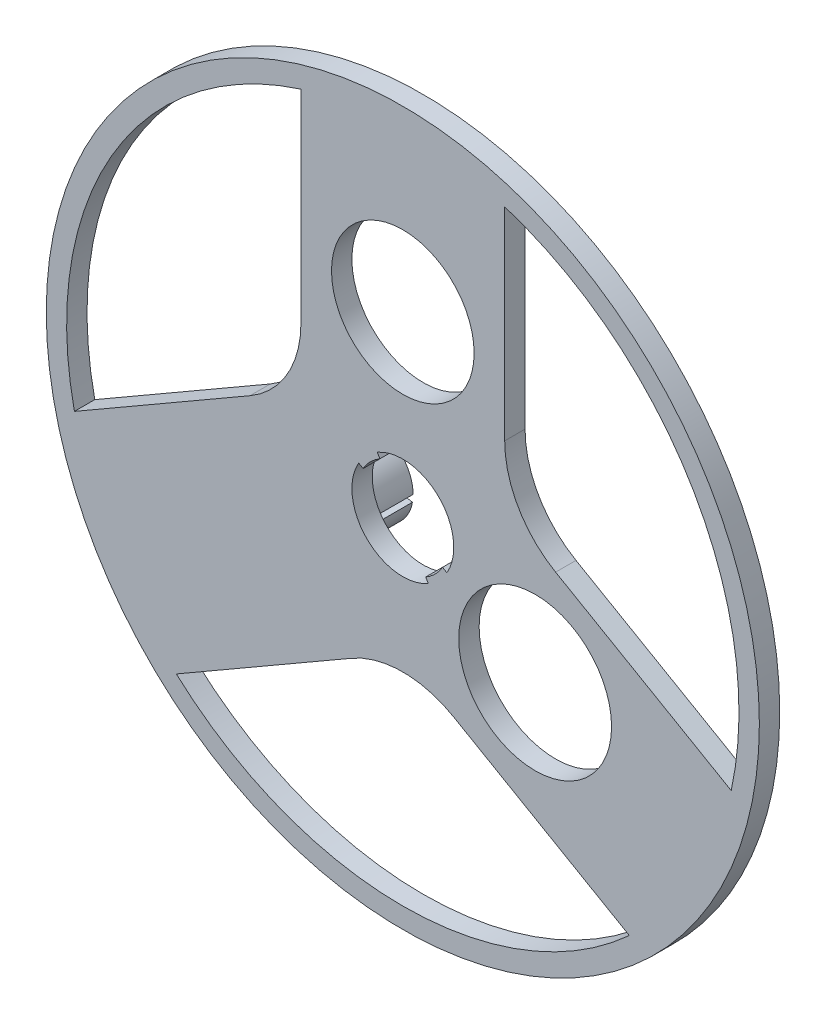
SolidWorks part; units mm, degrees
ref_plane "Front Plane" through (0, 0, 0) normal (0, 0, 1) x (1, 0, 0)
ref_plane "Top Plane" through (0, 0, 0) normal (0, 1, 0) x (1, 0, 0)
ref_plane "Right Plane" through (0, 0, 0) normal (1, 0, 0) x (0, 0, -1)
sketch "Sketch1" plane through (0, 0, 0) normal (0, 0, 1) x (1, 0, 0)
  line L0 (0, 0) -> (0, 33) construction
  line L1 (0, 0) -> (-10, 5.7735)
  line L2 (-10, 5.7735) -> (-10, 31.4484)
  line L3 (0, 0) -> (10, 5.7735)
  line L4 (10, 5.7735) -> (10, 31.4484)
  line L5 (10, 5.7735) -> (32.2351, -7.0639)
  line L6 (0, -11.547) -> (22.2351, -24.3844)
  line L7 (0, 0) -> (0, -11.547)
  line L8 (0, 0) -> (10, 5.7735)
  line L9 (0, -11.547) -> (-22.2351, -24.3844)
  line L10 (-10, 5.7735) -> (-32.2351, -7.0639)
  line L11 (0, 0) -> (-10, 5.7735)
  line L12 (0, 0) -> (0, -11.547)
  circle A0 centre (0, 0) radius 35
  circle A2 centre (0, 0) radius 33
  point P20 (0, 0)
  dimension "D1" = 70
  dimension "D2" = 10
  dimension "D3" = 66
  dimension "D4" = 60
  dimension "D5" = 3
extrude "Boss-Extrude1" add sketch "Sketch1" along normal blind 2 contours L1 L0 A2 L2 | L0 L3 L4 A2 | L6 A2 L5 L3 L7 | L10 A2 L9 L7 L1 | A0 A2 L9 region at (-4.794, 17.6439, 0) region at (-15.2801, -8.822, 0) region at (4.794, 17.6439, 0) region at (15.2801, -8.822, 0) region at (-34.0101, 0, 0)
fillet "Fillet1" radius 10 3 edges at (10, 5.7735, 1) (0, -11.547, 1) (-10, 5.7735, 1)
sketch "Sketch3" plane through (0, 0, 0) normal (0, 0, -1) x (-1, 0, 0)
  line L0 (0, 0) -> (0, 35) construction
  line L1 (0, 0) -> (30.3109, -17.5) construction
  line L2 (0, 0) -> (-30.3109, -17.5) construction
  line L3 (-5, -14.4338) -> (-22.2351, -24.3844) construction
  line L4 (5, -14.4338) -> (22.2351, -24.3844) construction
  line L5 (12.9904, -7.5) -> (12.9904, -3.5)
  line L6 (12.9904, -7.5) -> (16.9296, -6.8054)
  line L7 (12.9904, -7.5) -> (13.685, -11.4392)
  line L8 (12.9904, -7.5) -> (16.9904, -7.5)
  line L9 (12.9904, -7.5) -> (9.0512, -8.1946)
  line L10 (12.9904, -7.5) -> (12.9904, -11.5)
  line L11 (12.9904, -7.5) -> (12.2958, -3.5608)
  line L12 (12.9904, -7.5) -> (8.9904, -7.5)
  circle A0 centre (0, 0) radius 15 construction
  circle A1 centre (0, 0) radius 35 construction
  circle A2 centre (0, 17.5) radius 7
  circle A3 centre (-12.9904, -7.5) radius 7.5
  circle A4 centre (12.9904, -7.5) radius 3.4
  circle A5 centre (12.9904, -7.5) radius 4
  point P31 (12.9904, -7.5)
  dimension "D1" = 30
  dimension "D2" = 14
  dimension "D3" = 15
  dimension "D4" = 6.8
  dimension "D5" = 8
  dimension "D6" = 80
  dimension "D7" = 4
sketch "Sketch2" plane through (0, 0, 0) normal (0, 0, -1) x (-1, 0, 0)
  line L0 (0, 0) -> (0, 35) construction
  line L1 (0, 0) -> (2.5, 4.3301) construction
  line L2 (0, 0) -> (4.3301, 2.5) construction
  line L3 (2.5, 4.3301) -> (2.25, 3.8971)
  line L4 (4.3301, 2.5) -> (3.8971, 2.25)
  line L5 (-2.5, -4.3301) -> (-2.25, -3.8971)
  line L6 (-4.3301, -2.5) -> (-3.8971, -2.25)
  circle A0 centre (0, 0) radius 5
  circle A1 centre (0, 0) radius 35 construction
  circle A2 centre (0, 0) radius 4.5
  point P19 (0, 0)
  dimension "D1" = 10
  dimension "D2" = 9
  dimension "D3" = 30
  dimension "D4" = 60
  dimension "D5" = 2
extrude "Cut-Extrude2" cut sketch "Sketch2" against normal up to next contours A2 | A2 L5 A0 L4 | A2 L3 A0 L6 region at (-2.2831, 4.1667, 0) region at (0, 0, 0) region at (-4.7272, 1.2666, 0)
extrude "Cut-Extrude3" cut sketch "Sketch3" against normal up to next contours A3 | A2 region at (0, 17.5, 0) region at (12.9904, -7.5, 0)
extrude "Boss-Extrude2" add sketch "Sketch3<4>" along normal blind 8 contours L7 A5 L8 A4 | L6 A5 L5 A4 | L11 A5 L12 A4 | L9 A5 L10 A4 region at (-15.185, -4.8846, 0) region at (-15.6058, -9.6946, 0) region at (-10.7958, -10.1154, 0) region at (-10.375, -5.3054, 0)
sketch "Sketch3<4>" plane through (0, 0, 0) normal (0, 0, -1) x (-1, 0, 0) same geometry as "Sketch3"
